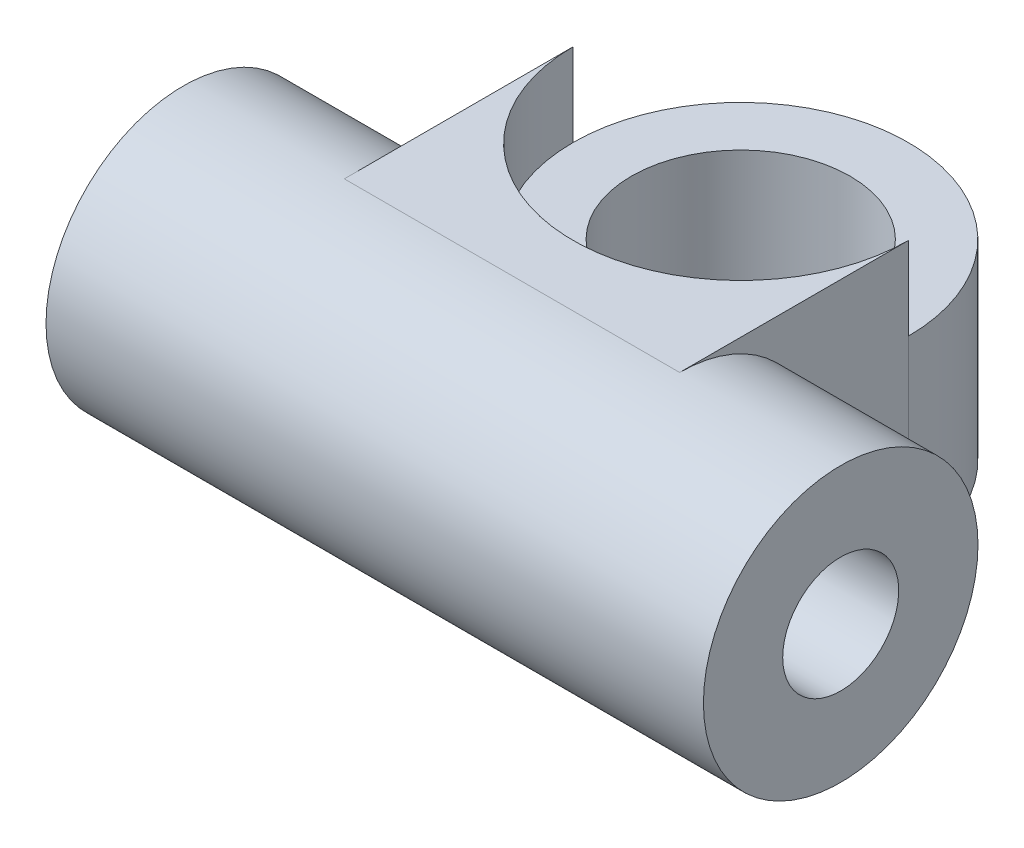
SolidWorks part; units mm, degrees
ref_plane "Piano frontale" through (0, 0, 0) normal (0, 0, 1) x (1, 0, 0)
ref_plane "Piano superiore" through (0, 0, 0) normal (0, 1, 0) x (1, 0, 0)
ref_plane "Piano destro" through (0, 0, 0) normal (1, 0, 0) x (0, 0, -1)
sketch "Schizzo1" plane through (0, 0, 0) normal (1, 0, 0) x (0, 0, -1)
  circle A1 centre (0, 0) radius 2.485
  dimension "D2" = 4.97
extrude "Estrusione-Estrusione1" add sketch "Schizzo1" along normal blind 11.9
sketch "Schizzo2" plane through (0, 0, 0) normal (0, 1, 0) x (1, 0, 0)
  line L0 (2.915, 4.14) -> (2.915, 0)
  line L2 (8.985, 4.14) -> (8.985, 0)
  line L4 (2.915, 0) -> (8.985, 0)
  line L5 (5.95, 2.485) -> (5.95, 7.175) construction
  line L6 (11.9, 2.485) -> (0, 2.485) construction
  circle A1 centre (5.95, 4.14) radius 3.035
  point P5 (5.95, 7.175)
  dimension "D2" = 6.07
  dimension "D3" = 9.66
extrude "Estrusione-Estrusione2" add sketch "Schizzo2" along normal mid plane 4.97 contours A1 | A1 L0 L4 L2 region at (5.95, 0, -1.0088) region at (5.95, 0, -4.14)
sketch "Schizzo3" plane through (0, 2.485, 0) normal (0, 1, 0) x (1, 0, 0)
  circle A0 centre (5.95, 4.14) radius 1.98
  dimension "D1" = 3.96
extrude "Taglio-Estrusione1" cut sketch "Schizzo3" against normal through all
sketch "Schizzo4" plane through (0, 0, 0) normal (-1, 0, 0) x (0, 0, 1)
  circle A0 centre (0, 0) radius 1.05
  dimension "D1" = 2.1
extrude "Taglio-Estrusione2" cut sketch "Schizzo4" against normal through all
sketch "Schizzo5" plane through (0, 2.485, 0) normal (0, 1, 0) x (1, 0, 0)
  circle A0 centre (5.95, 4.14) radius 3.035
  arc A1 (8.985, 4.14) -> (2.915, 4.14) centre (5.95, 4.14) ccw construction
extrude "Taglio-Estrusione3" cut sketch "Schizzo5" against normal blind 1.5
